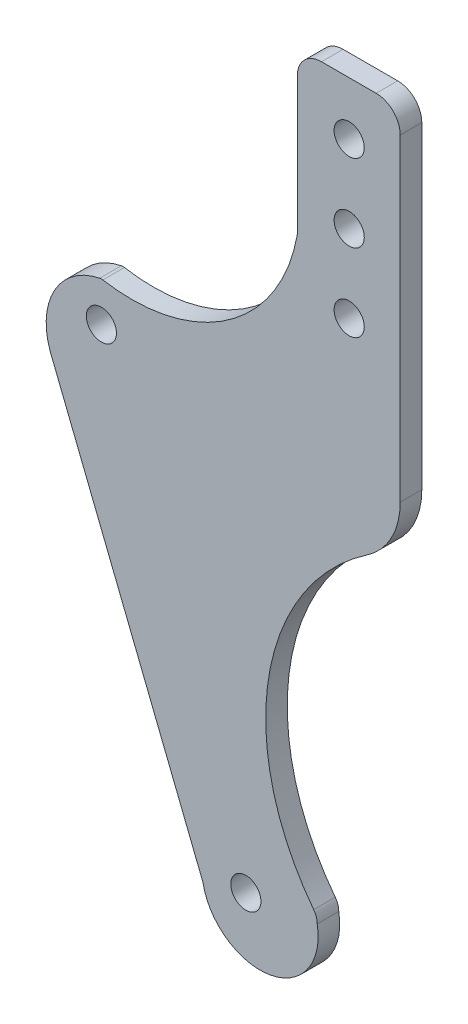
SolidWorks part; units mm, degrees
ref_plane "Front Plane" through (0, 0, 0) normal (0, 0, 1) x (1, 0, 0)
ref_plane "Top Plane" through (0, 0, 0) normal (0, 1, 0) x (1, 0, 0)
ref_plane "Right Plane" through (0, 0, 0) normal (1, 0, 0) x (0, 0, -1)
sketch "Sketch1" plane through (0, 0, 0) normal (0, 0, 1) x (1, 0, 0)
  line L0 (0, 0) -> (0, 30.156) construction
  line L1 (0, 0) -> (32.4691, 0) construction
  line L3 (-26.683, 26.3577) -> (-26.683, 6.3518)
  line L4 (-15.0841, 29.9137) -> (-23.127, 29.9137)
  line L5 (-63.1034, -26.9607) -> (-40.5959, -83.4559)
  line L7 (-11.5281, -20.4623) -> (-11.5281, 26.3577)
  line L8 (-40.5959, -83.4559) -> (-24.2809, -78.8021) construction
  circle A0 centre (-55.5441, -19.825) radius 2.2225
  circle A1 centre (-19.05, 22.085) radius 2.2225
  circle A2 centre (-19.05, -0.775) radius 2.2225
  arc A6 (-15.0841, 29.9137) -> (-11.5281, 26.3577) centre (-15.0841, 26.3577) cw
  arc A7 (-23.127, 29.9137) -> (-26.683, 26.3577) centre (-23.127, 26.3577) ccw
  arc A9 (-16.357, -29.5947) -> (-24.2809, -78.8021) centre (2.9569, -57.9465) ccw
  arc A11 (-16.357, -29.5947) -> (-11.5281, -20.4623) centre (-22.5782, -20.4623) ccw
  circle A14 centre (-34.2687, -81.6511) radius 2.2225
  arc A17 (-23.7579, -80.3848) -> (-24.2809, -78.8021) centre (-26.2976, -80.3463) ccw
  arc A21 (-40.5959, -83.4559) -> (-23.7579, -80.3848) centre (-32.1769, -81.9204) ccw
  arc A23 (-63.1034, -26.9607) -> (-55.7802, -14.0251) centre (-53.8578, -23.6541) cw
  circle A24 centre (-19.05, 10.655) radius 2.2225
  arc A25 (-55.3282, -14.0195) -> (-26.7251, 5.891) centre (-51.0844, 10.3846) ccw
  arc A26 (-55.3282, -14.0195) -> (-55.7802, -14.0251) centre (-55.5392, -15.2326) ccw
  arc A27 (-26.683, 6.3518) -> (-26.7251, 5.891) centre (-29.223, 6.3518) cw
  point P14 (-19.1056, 29.9137)
  point P24 (-15.2948, 26.5068)
  point P35 (-55.5441, -13.981)
  point P40 (-55.3282, -14.0251)
  point P41 (-55.5441, -13.981)
  dimension "D1" = 4.445
  dimension "D2" = 2.54
  dimension "D3" = 3.556
  dimension "D4" = 34.3053
  dimension "D5" = 11.0501
  dimension "D6" = 8.5579
  dimension "D7" = 9.8191
  dimension "D11" = 11.5281
  dimension "D12" = 15.2948
  dimension "D13" = 19.05
  dimension "D10" = 2.9569
  dimension "D14" = 19.1056
  dimension "D15" = 24.2809
  dimension "D18" = 53.8578
  dimension "D19" = 55.3282
  dimension "D21" = 26.5068
  dimension "D22" = 29.9137
  dimension "D23" = 32.1769
  dimension "D24" = 34.2687
  dimension "D8" = 24.7703
  dimension "D9" = 1.2313
  dimension "D16" = 26.7251
  dimension "D17" = 23.7579
  dimension "D20" = 5.891
  dimension "D25" = 40.5959
  dimension "D26" = 10.655
  dimension "D27" = 22.085
  dimension "D28" = 20.4623
  dimension "D30" = 0.775
  dimension "D32" = 63.1034
  dimension "D36" = 19.825
extrude "Boss-Extrude1" add sketch "Sketch1" along normal blind 3.175
